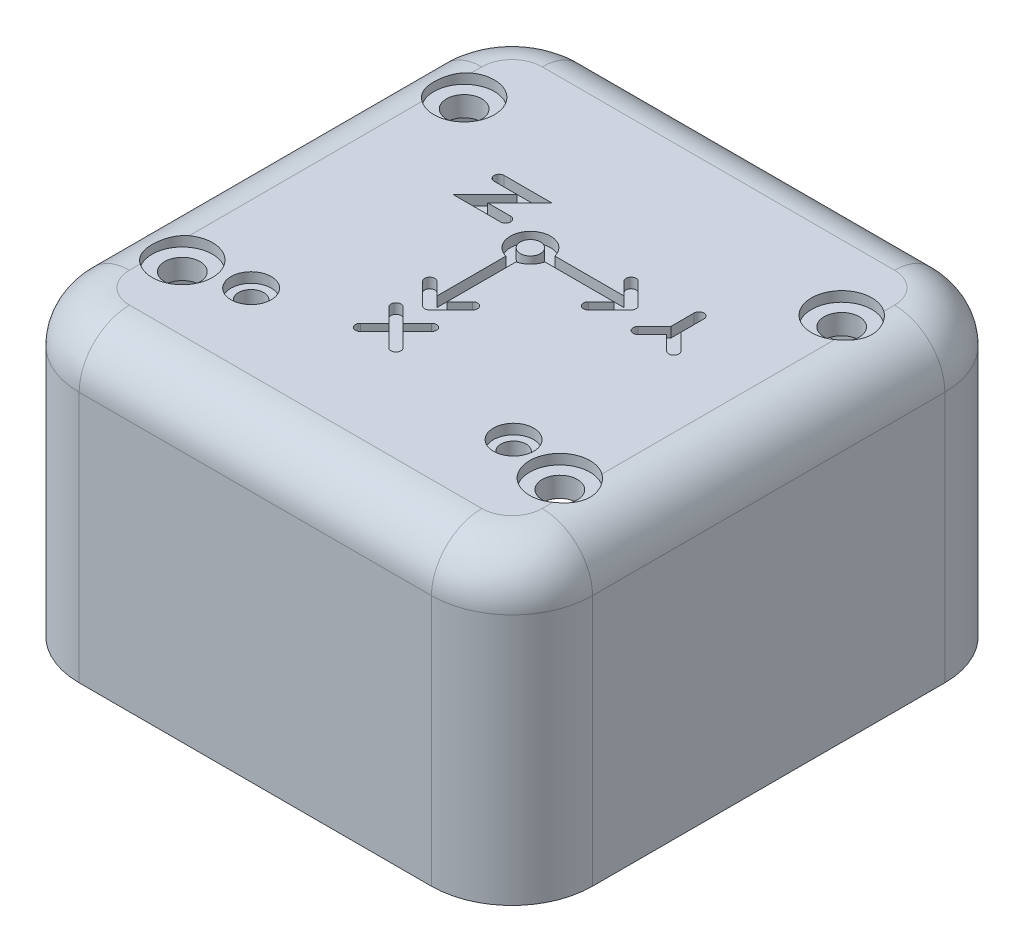
SolidWorks part; units mm, degrees
ref_plane "Front Plane" through (0, 0, 0) normal (0, 0, 1) x (1, 0, 0)
ref_plane "Top Plane" through (0, 0, 0) normal (0, 1, 0) x (1, 0, 0)
ref_plane "Right Plane" through (0, 0, 0) normal (1, 0, 0) x (0, 0, -1)
sketch "Sketch1" plane through (0, 0, 0) normal (0, 1, 0) x (1, 0, 0)
  line L1 (8, 0) -> (43, 0)
  line L2 (0, 8) -> (0, 43)
  line L3 (8, 51) -> (43, 51)
  line L4 (51, 8) -> (51, 43)
  arc A0 (43, 51) -> (51, 43) centre (43, 43) cw
  arc A1 (43, 0) -> (51, 8) centre (43, 8) ccw
  arc A2 (8, 0) -> (0, 8) centre (8, 8) cw
  arc A3 (0, 43) -> (8, 51) centre (8, 43) cw
  point P7 (51, 51)
  point P10 (51, 0)
  point P13 (0, 0)
  point P16 (0, 51)
  dimension "D3" = 8
  dimension "D1" = 51
  dimension "D2" = 51
extrude "Boss-Extrude1" add sketch "Sketch1" along normal blind 30
sketch "Sketch2" plane through (0, 0, 0) normal (0, -1, 0) x (1, 0, 0)
  line L0 (8, 0) -> (43, 0) construction
  line L1 (8, -2) -> (43, -2)
  line L2 (2, -8) -> (2, -43)
  line L3 (8, -49) -> (43, -49)
  line L4 (49, -8) -> (49, -43)
  line L5 (51, -8) -> (51, -43) construction
  line L6 (43, -51) -> (8, -51) construction
  line L7 (0, -43) -> (0, -8) construction
  arc A0 (43, -49) -> (49, -43) centre (43, -43) ccw
  arc A1 (2, -43) -> (8, -49) centre (8, -43) ccw
  arc A2 (43, -2) -> (49, -8) centre (43, -8) cw
  arc A3 (8, -2) -> (2, -8) centre (8, -8) ccw
  dimension "D5" = 6
  dimension "D1" = 2
  dimension "D2" = 2
  dimension "D3" = 2
  dimension "D4" = 2
extrude "Cut-Extrude1" cut sketch "Sketch2" against normal blind 27
sketch "Sketch3" plane through (0, 27, 0) normal (0, -1, 0) x (1, 0, 0)
  line L0 (43, -2) -> (8, -2) construction
  line L1 (9.5, -3.5) -> (41.5, -3.5) construction
  line L2 (3.5, -9.5) -> (3.5, -41.5) construction
  line L3 (9.5, -47.5) -> (41.5, -47.5) construction
  line L4 (47.5, -9.5) -> (47.5, -41.5) construction
  line L5 (2, -8) -> (2, -43) construction
  line L6 (8, -49) -> (43, -49) construction
  line L7 (49, -43) -> (49, -8) construction
  line L8 (25.5, -3.5) -> (25.5, -47.5) construction
  line L21 (3.5, -25.5) -> (47.5, -25.5) construction
  line L23 (9.915, -49) -> (41.085, -49) construction
  line L24 (9.915, -49) -> (9.915, -10) construction
  line L25 (9.915, -10) -> (41.085, -10) construction
  line L26 (41.085, -49) -> (41.085, -10) construction
  arc A0 (41.5, -3.5) -> (47.5, -9.5) centre (41.5, -9.5) cw construction
  arc A1 (41.5, -47.5) -> (47.5, -41.5) centre (41.5, -41.5) ccw construction
  arc A2 (3.5, -41.5) -> (9.5, -47.5) centre (9.5, -41.5) ccw construction
  arc A3 (9.5, -3.5) -> (3.5, -9.5) centre (9.5, -9.5) ccw construction
  circle A4 centre (6.75, -11.5) radius 3.25 construction
  circle A5 centre (6.75, -11.5) radius 1.75
  circle A6 centre (44.25, -11.5) radius 3.25 construction
  circle A7 centre (44.25, -11.5) radius 1.75
  circle A8 centre (44.25, -39.5) radius 3.25 construction
  circle A9 centre (44.25, -39.5) radius 1.75
  circle A10 centre (6.75, -39.5) radius 3.25 construction
  circle A11 centre (6.75, -39.5) radius 1.75
  circle A12 centre (38.655, -12.5) radius 1.25
  circle A13 centre (12.585, -12.5) radius 1.25
  dimension "D5" = 6
  dimension "D6" = 6.5
  dimension "D8" = 3.5
  dimension "D13" = 2.5
  dimension "D16" = 2.5
  dimension "D18" = 26.07
  dimension "D1" = 1.5
  dimension "D2" = 1.5
  dimension "D3" = 1.5
  dimension "D4" = 1.5
  dimension "D7" = 3.25
  dimension "D9" = 8
  dimension "D10" = 31.17
  dimension "D11" = 39
  dimension "D12" = 15.585
  dimension "D14" = 2.43
  dimension "D15" = 2.5
  dimension "D17" = 2.5
extrude "Cut-Extrude2" cut sketch "Sketch3" against normal blind 3
sketch "Sketch4" plane through (0, 30, 0) normal (0, 1, 0) x (1, 0, 0)
  circle A0 centre (44.25, 39.5) radius 3
  circle A1 centre (6.75, 39.5) radius 3
  circle A2 centre (6.75, 11.5) radius 3
  circle A3 centre (12.585, 12.5) radius 2
  circle A4 centre (38.655, 12.5) radius 2
  circle A5 centre (44.25, 11.5) radius 3
  dimension "D1" = 6
  dimension "D2" = 6
  dimension "D3" = 6
  dimension "D4" = 6
  dimension "D5" = 4
  dimension "D6" = 4
extrude "Cut-Extrude3" cut sketch "Sketch4" against normal blind 1
sketch "Sketch5" plane through (0, 0, -49) normal (0, 0, 1) x (1, 0, 0)
  line L0 (8, 15) -> (43, 15) construction
  line L1 (8, 27) -> (8, 0) construction
  line L2 (43, 27) -> (43, 0) construction
  line L3 (8, 27) -> (43, 27) construction
  line L4 (9.915, 15) -> (9.915, 27) construction
  line L5 (9.585, 18) -> (34.085, 18)
  line L6 (8.585, 17) -> (8.585, 14)
  line L7 (9.585, 13) -> (34.085, 13)
  line L8 (35.085, 17) -> (35.085, 14)
  line L9 (41.085, 15) -> (41.085, 27) construction
  line L10 (25.5, 27) -> (25.5, 15) construction
  arc A0 (34.085, 18) -> (35.085, 17) centre (34.085, 17) cw
  arc A1 (34.085, 13) -> (35.085, 14) centre (34.085, 14) ccw
  arc A2 (8.585, 14) -> (9.585, 13) centre (9.585, 14) ccw
  arc A3 (9.585, 18) -> (8.585, 17) centre (9.585, 17) ccw
  point P20 (35.085, 18)
  point P25 (8.585, 13)
  point P28 (8.585, 18)
  dimension "D8" = 1
  dimension "D1" = 12
  dimension "D2" = 5
  dimension "D3" = 2
  dimension "D4" = 16.915
  dimension "D5" = 15.585
  dimension "D6" = 15.585
  dimension "D7" = 6
extrude "Cut-Extrude4" cut sketch "Sketch5" against normal blind 2
fillet "Fillet1" radius 5 8 edges at (48.6569, 30, -2.3431) (25.5, 30, 0) (2.3431, 30, -2.3431) (0, 30, -25.5) (2.3431, 30, -48.6569) (25.5, 30, -51) (48.6569, 30, -48.6569) (51, 30, -25.5)
fillet "Fillet2" radius 1.5 8 edges at (47.2426, 27, -47.2426) (25.5, 27, -49) (3.7574, 27, -47.2426) (2, 27, -25.5) (3.7574, 27, -3.7574) (25.5, 27, -2) (47.2426, 27, -3.7574) (49, 27, -25.5)
sketch "Sketch6" plane through (0, 30, 0) normal (0, 1, 0) x (1, 0, 0)
  line L1 (24.9204, 29.3484) -> (31.7768, 29.3484)
  line L2 (24.9204, 30.3484) -> (31.7768, 30.3484)
  line L3 (23.1569, 17.0253) -> (21.7427, 18.4395)
  line L4 (23.4839, 27.9119) -> (23.4839, 21.0555)
  line L8 (23.3375, 19.4949) -> (25.4588, 21.6162)
  line L9 (22.4839, 21.0555) -> (21.2162, 22.3233)
  line L10 (31.7768, 29.3484) -> (30.509, 28.0807)
  line L11 (33.3375, 30.202) -> (31.2162, 32.3233)
  line L14 (23.4839, 21.0555) -> (24.7517, 22.3233)
  line L15 (22.6304, 19.4949) -> (20.509, 21.6162)
  line L16 (33.3375, 29.4949) -> (31.2162, 27.3736)
  line L17 (31.7768, 30.3484) -> (30.509, 31.6162)
  line L18 (22.4839, 27.9119) -> (22.4839, 21.0555)
  line L24 (25.2782, 14.904) -> (23.864, 16.3182)
  line L25 (21.7427, 14.1969) -> (23.1569, 15.6111)
  line L26 (39.3465, 28.435) -> (37.7252, 30.0564)
  line L27 (36.7252, 30.0564) -> (35.1039, 28.435)
  line L28 (37.7252, 30.0564) -> (37.7252, 32.3493)
  line L29 (19.277, 31.5842) -> (16.9841, 31.5842)
  line L30 (16.9841, 31.5842) -> (20.1661, 34.7662)
  line L31 (20.1661, 34.7662) -> (15.4553, 34.7662)
  line L32 (24.5711, 14.1969) -> (23.1569, 15.6111)
  line L33 (21.0356, 14.904) -> (22.4498, 16.3182)
  line L34 (38.6394, 27.7279) -> (37.2252, 29.1421)
  line L35 (37.2252, 29.1421) -> (35.811, 27.7279)
  line L36 (36.7252, 30.0564) -> (36.7252, 32.3493)
  line L37 (19.277, 30.5842) -> (14.5699, 30.5842)
  line L38 (14.5699, 30.5842) -> (17.7519, 33.7662)
  line L39 (17.7519, 33.7662) -> (15.4553, 33.7662)
  line L41 (23.864, 16.3182) -> (25.2782, 17.7324)
  line L45 (23.1569, 17.0253) -> (24.5711, 18.4395)
  line L47 (22.4498, 16.3182) -> (21.0356, 17.7324)
  arc A1 (23.4839, 27.9119) -> (24.9204, 29.3484) centre (22.9839, 29.8484) ccw
  circle A2 centre (22.9839, 29.8484) radius 1
  arc A3 (33.3375, 30.202) -> (33.3375, 29.4949) centre (32.9839, 29.8484) cw
  arc A4 (22.6304, 19.4949) -> (23.3375, 19.4949) centre (22.9839, 19.8484) ccw
  arc A5 (23.3375, 19.4949) -> (22.6304, 19.4949) centre (22.9839, 19.8484) cw
  arc A6 (25.4588, 21.6162) -> (24.7517, 22.3233) centre (25.1052, 21.9698) ccw
  arc A7 (23.3375, 19.4949) -> (22.6304, 19.4949) centre (22.9839, 19.8484) cw
  arc A8 (21.2162, 22.3233) -> (20.509, 21.6162) centre (20.8626, 21.9698) ccw
  arc A9 (33.3375, 30.202) -> (33.3375, 29.4949) centre (32.9839, 29.8484) cw
  arc A10 (30.509, 28.0807) -> (31.2162, 27.3736) centre (30.8626, 27.7271) ccw
  arc A11 (33.3375, 30.202) -> (33.3375, 29.4949) centre (32.9839, 29.8484) cw
  arc A12 (31.2162, 32.3233) -> (30.509, 31.6162) centre (30.8626, 31.9698) ccw
  arc A13 (25.2782, 14.904) -> (24.5711, 14.1969) centre (24.9247, 14.5504) cw
  arc A14 (24.9204, 30.3484) -> (22.4839, 27.9119) centre (22.9839, 29.8484) ccw
  arc A15 (21.7427, 18.4395) -> (21.0356, 17.7324) centre (21.3891, 18.086) ccw
  arc A16 (21.7427, 14.1969) -> (21.0356, 14.904) centre (21.3891, 14.5504) cw
  arc A17 (25.2782, 17.7324) -> (24.5711, 18.4395) centre (24.9247, 18.086) ccw
  arc A18 (39.3465, 28.435) -> (38.6394, 27.7279) centre (38.993, 28.0815) cw
  arc A21 (35.1039, 28.435) -> (35.811, 27.7279) centre (35.4574, 28.0815) ccw
  arc A23 (37.7252, 32.3493) -> (36.7252, 32.3493) centre (37.2252, 32.3493) ccw
  arc A24 (19.277, 31.5842) -> (19.277, 30.5842) centre (19.277, 31.0842) cw
  arc A25 (15.4553, 34.7662) -> (15.4553, 33.7662) centre (15.4553, 34.2662) ccw
extrude "Cut-Extrude5" cut sketch "Sketch6" against normal blind 1 contours L2 A14 L18 L9 A8 L15 A4 L8 A6 L14 L4 A1 L1 L10 A10 L16 A3 L11 A12 L17 A2 | L31 A25 L39 L38 L37 A24 L29 L30 | L28 A23 L36 L27 A21 L35 L34 A18 L26 | L41 A17 L45 L3 A15 L47 L33 A16 L25 L32 A13 L24 region at (24.2669, 30, -28.5654) region at (23.1569, 30, -16.3182) region at (37.2252, 30, -29.6457) region at (17.3673, 30, -32.6757)
sketch "Sketch7" plane through (0, 0, -51) normal (0, 0, -1) x (-1, 0, 0)
  line L0 (-8.585, 17) -> (-8.585, 14) construction
  line L1 (-35.085, 23) -> (-8.585, 23)
  line L2 (-40.085, 18) -> (-40.085, 13)
  line L3 (-35.085, 8) -> (-8.585, 8)
  line L4 (-3.585, 18) -> (-3.585, 13)
  line L5 (-35.085, 14) -> (-35.085, 17) construction
  line L6 (-34.085, 18) -> (-9.585, 18) construction
  line L7 (-9.585, 13) -> (-34.085, 13) construction
  arc A0 (-8.585, 23) -> (-3.585, 18) centre (-8.585, 18) cw
  arc A1 (-8.585, 8) -> (-3.585, 13) centre (-8.585, 13) ccw
  arc A2 (-40.085, 13) -> (-35.085, 8) centre (-35.085, 13) ccw
  arc A3 (-35.085, 23) -> (-40.085, 18) centre (-35.085, 18) ccw
  dimension "D5" = 5
  dimension "D1" = 5
  dimension "D2" = 5
  dimension "D3" = 5
  dimension "D4" = 5
extrude "Cut-Extrude6" cut sketch "Sketch7" against normal blind 0.8
